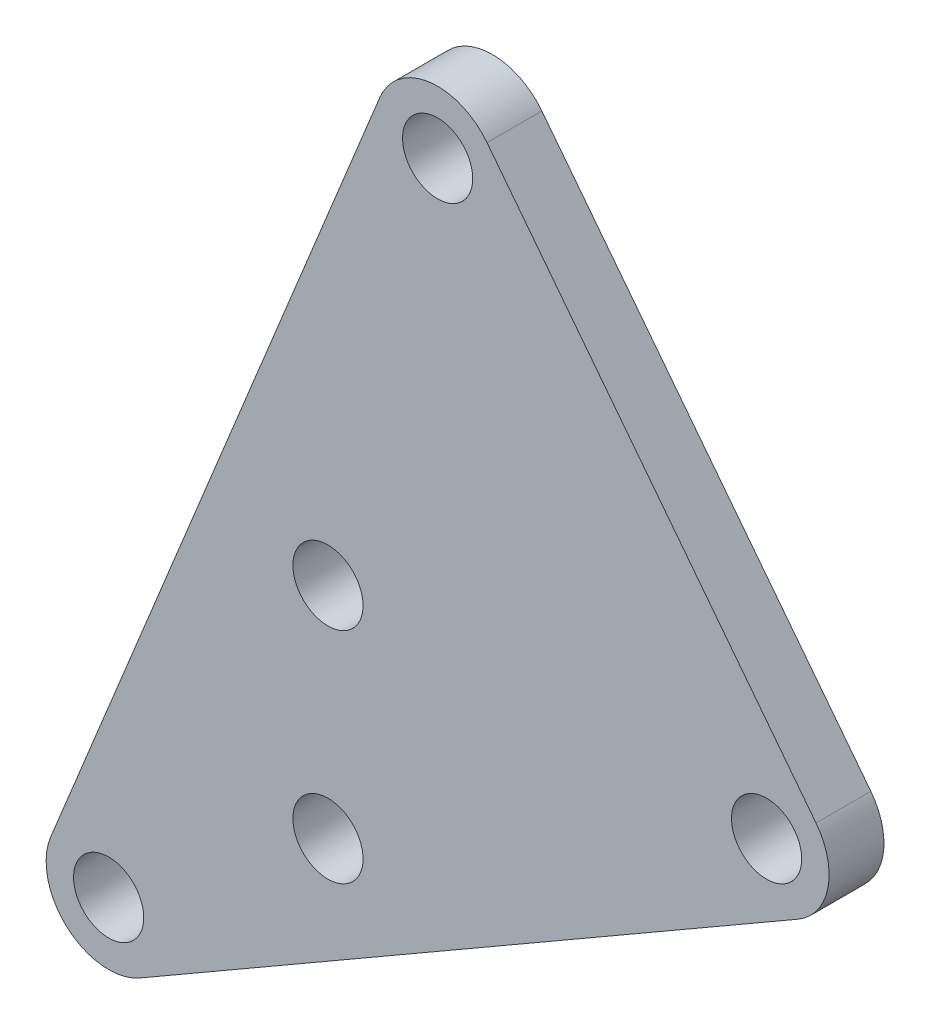
SolidWorks part; units mm, degrees
ref_plane "Front Plane" through (0, 0, 0) normal (0, 0, 1) x (1, 0, 0)
ref_plane "Top Plane" through (0, 0, 0) normal (0, 1, 0) x (1, 0, 0)
ref_plane "Right Plane" through (0, 0, 0) normal (1, 0, 0) x (0, 0, -1)
sketch "Sketch1" plane through (0, 0, 0) normal (0, 0, 1) x (1, 0, 0)
  line L3 (9.2115, 26.8099) -> (28.2615, 2.2165)
  line L6 (27.2097, -3.1346) -> (-10.8902, -25.1316)
  line L7 (2.9997, 25.9633) -> (-16.0503, -20.6272)
  circle A0 centre (0, 0) radius 2.032
  circle A1 centre (6.35, 24.5934) radius 2.032
  circle A2 centre (-12.7, -21.997) radius 2.032
  circle A3 centre (25.4, 0) radius 2.032
  arc A4 (9.2115, 26.8099) -> (2.9997, 25.9633) centre (6.35, 24.5934) ccw
  arc A5 (-16.0503, -20.6272) -> (-10.8902, -25.1316) centre (-12.7, -21.997) ccw
  arc A6 (27.2097, -3.1346) -> (28.2615, 2.2165) centre (25.4, 0) ccw
  circle A11 centre (0, -12.7) radius 2.032
  point P2 (-12.7, -25.613)
  point P10 (-15.0594, -19.2522)
  point P19 (-19.5946, -22.9974)
  point P21 (-15.2601, -19.4384)
  point P22 (5.7615, 24.9916)
  point P24 (4.318, 27.1529)
  point P25 (-3.7148, 15.0684)
  point P26 (11.7089, -21.4237)
  point P27 (9.8934, -20.6272)
  dimension "D3" = 7.239
  dimension "D4" = 4.064
  dimension "D6" = 12.7
  dimension "D1" = 25.4
  dimension "D2" = 25.4
  dimension "D5" = 25.4
  dimension "D7" = 6.35
  dimension "D9" = 12.7
extrude "Boss-Extrude1" add sketch "Sketch1" along normal blind 3.175
